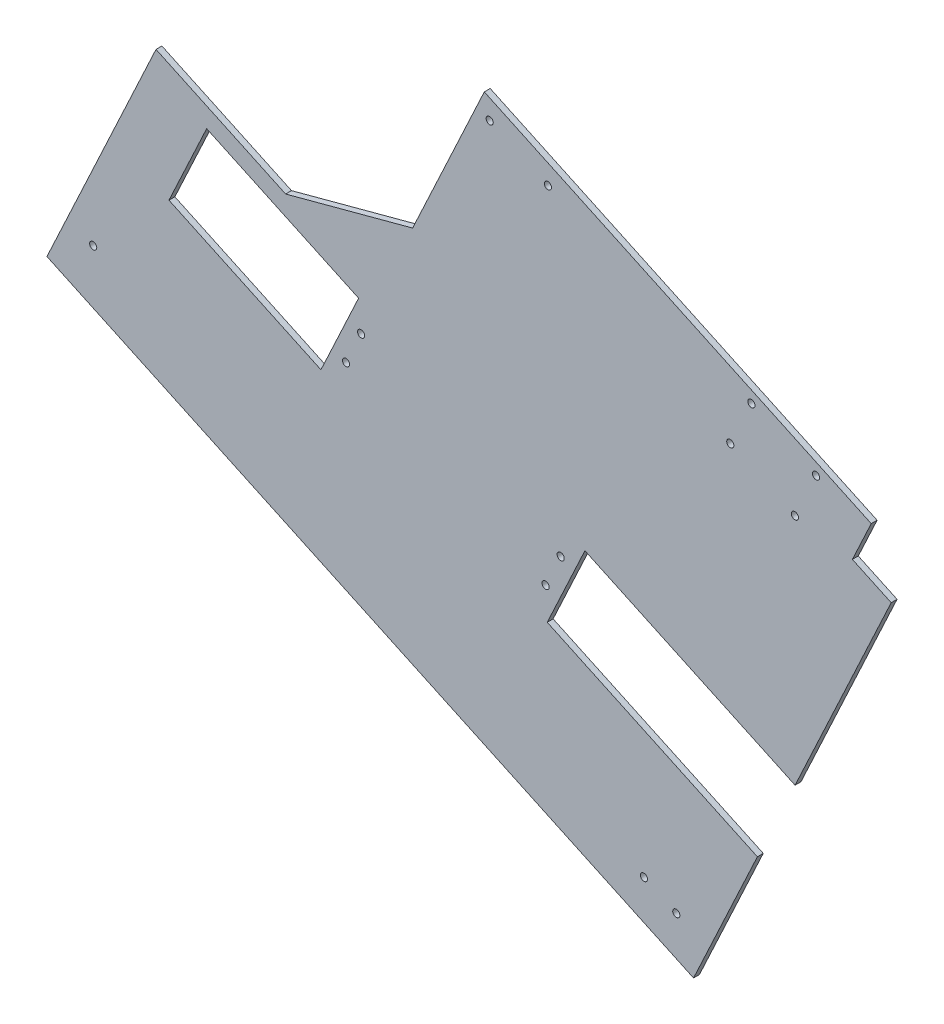
SolidWorks part; units mm, degrees
material "Balsa"
ref_plane "Front Plane" through (0, 0, 0) normal (0, 0, 1) x (1, 0, 0)
ref_plane "Top Plane" through (0, 0, 0) normal (0, 1, 0) x (1, 0, 0)
ref_plane "Right Plane" through (0, 0, 0) normal (1, 0, 0) x (0, 0, -1)
sketch "Sketch1" plane through (0, 0, 0) normal (0, 0, 1) x (1, 0, 0)
  line L0 (-299.6433, -82.65) -> (-127.3464, -36.4832)
  line L1 (-127.3464, -36.4832) -> (-87.1479, 49.7228)
  line L2 (-87.1479, 49.7228) -> (129.7831, -51.4338)
  line L3 (129.7831, -51.4338) -> (119.2177, -74.0915)
  line L4 (119.2177, -74.0915) -> (140.969, -84.2344)
  line L5 (140.969, -84.2344) -> (30.1585, -321.8683)
  line L6 (30.1585, -321.8683) -> (-332.3646, -152.8209)
  line L7 (-332.3646, -152.8209) -> (-299.6433, -82.65)
  line L9 (-332.3646, -152.8209) -> (-261.0998, 0.0069) construction
  line L10 (30.1585, -321.8683) -> (-332.3646, -152.8209) construction
  line L11 (140.969, -84.2344) -> (30.1585, -321.8683) construction
  line L12 (-189.2372, 97.3278) -> (129.7831, -51.4338) construction
  line L13 (119.2177, -74.0915) -> (140.969, -84.2344) construction
  line L14 (129.7831, -51.4338) -> (119.2177, -74.0915) construction
  line L15 (-110.3324, 0.0035) -> (-87.1479, 49.7228) construction
  line L17 (-198.5484, -55.5617) -> (-44.0003, -14.1506) construction
  line L18 (-198.5484, -55.5617) -> (-271.2117, -21.6782)
  line L19 (-271.2117, -21.6782) -> (-299.6433, -82.65)
  line L20 (-271.2117, -21.6782) -> (-198.5484, -55.5617) construction
  circle A0 centre (87.0035, -69.0002) radius 2
  circle A1 centre (98.8369, -43.6236) radius 2
  circle A2 centre (62.5845, -26.7189) radius 2
  circle A3 centre (50.7512, -52.0955) radius 2
  circle A4 centre (2.3586, -286.8374) radius 2
  circle A5 centre (-306.4229, -134.5749) radius 2
  circle A6 centre (20.4847, -295.2897) radius 2
  circle A7 centre (2.3586, -286.8374) radius 2 construction
  circle A8 centre (20.4847, -295.2897) radius 2 construction
  dimension "D1" = 4
  dimension "D2" = 4
  dimension "D3" = 4
  dimension "D4" = 4
  dimension "D7" = 4
  dimension "D5" = 27.5
  dimension "D6" = 15.8
extrude "Boss-Extrude1" add sketch "Sketch1" along normal blind 3.3 contours L7 L6 L5 L4 L3 L2 L1 L0 A6 A5 A4 A3 A2 A1 A0 | L18 L19 L0 region at (-256.4678, -53.2966, 0) region at (-69.6087, -133.5527, 0)
sketch "Sketch2" plane through (0, 0, 3.3) normal (0, 0, -1) x (-1, 0, 0)
  line L2 (87.1479, 49.7228) -> (-129.7831, -51.4338) construction
  line L3 (127.3464, -36.4832) -> (87.1479, 49.7228) construction
  circle A0 centre (51.4966, 22.0645) radius 2
  circle A1 centre (84.1237, 37.2788) radius 2
  dimension "D1" = 4
  dimension "D2" = 4
  dimension "D3" = 10
  dimension "D4" = 36
  dimension "D5" = 10
  dimension "D6" = 8
extrude "Cut-Extrude1" cut sketch "Sketch2" along normal blind 10 contours A0 | A1 region at (-51.4966, 22.0645, 3.3) region at (-84.1237, 37.2788, 3.3)
sketch "Sketch5" plane through (0, 0, 0) normal (0, 0, 1) x (1, 0, 0)
  line L0 (65.9543, -245.104) -> (-51.8657, -190.1636)
  line L2 (-51.8657, -190.1636) -> (-30.7348, -144.8482)
  line L3 (-30.7348, -144.8482) -> (87.0852, -199.7886)
  line L4 (87.0852, -199.7886) -> (65.9543, -245.104)
  line L7 (119.2177, -74.0915) -> (140.969, -84.2344) construction
  line L8 (140.969, -84.2344) -> (30.1585, -321.8683) construction
  dimension "D1" = 130
  dimension "D2" = 127.5
  dimension "D3" = 50
extrude "Cut-Extrude2" cut sketch "Sketch5" along normal blind 10
sketch "Sketch6" plane through (0, 0, 3.3) normal (0, 0, 1) x (1, 0, 0)
  line L0 (-178.7488, -130.9971) -> (-157.6179, -85.6817)
  line L1 (-157.6179, -85.6817) -> (-242.8108, -45.9555)
  line L2 (-242.8108, -45.9555) -> (-263.9417, -91.2709)
  line L3 (-263.9417, -91.2709) -> (-178.7488, -130.9971)
  line L4 (-332.3646, -152.8209) -> (-271.2117, -21.6782) construction
  line L9 (65.9543, -245.104) -> (-51.8657, -190.1636) construction
  line L10 (-30.7348, -144.8482) -> (87.0852, -199.7886) construction
  dimension "D1" = 130
  dimension "D2" = 94
extrude "Cut-Extrude3" cut sketch "Sketch6" against normal blind 10
sketch "Sketch7" plane through (0, 0, 3.3) normal (0, 0, 1) x (1, 0, 0)
  circle A0 centre (-52.7985, -172.5711) radius 2
  circle A1 centre (-44.3462, -154.4449) radius 2
  circle A2 centre (-164.6725, -120.4034) radius 2
  circle A3 centre (-156.2202, -102.2772) radius 2
  circle A4 centre (-52.7985, -172.5711) radius 2 construction
  circle A5 centre (-44.3462, -154.4449) radius 2 construction
  circle A6 centre (-164.6725, -120.4034) radius 2 construction
  circle A7 centre (-156.2202, -102.2772) radius 2 construction
extrude "Cut-Extrude4" cut sketch "Sketch7" against normal blind 10
